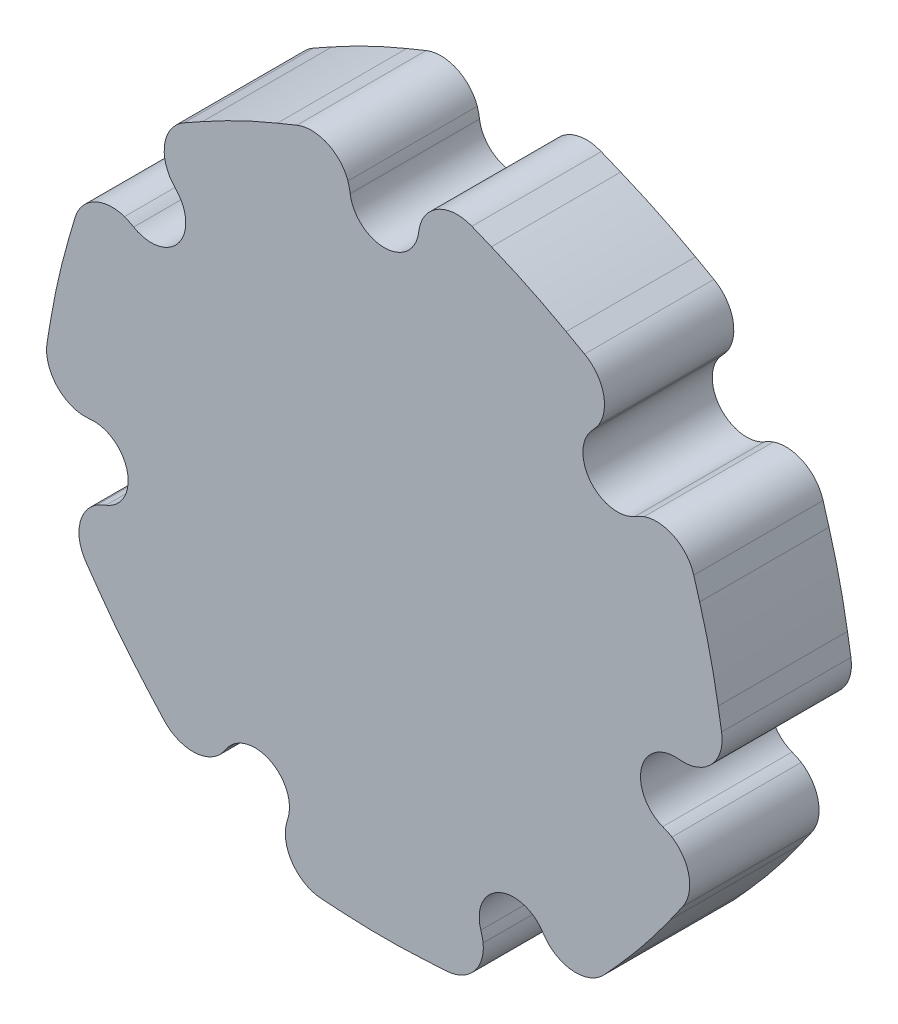
SolidWorks part; units mm, degrees
ref_plane "Piano frontale" through (0, 0, 0) normal (0, 0, 1) x (1, 0, 0)
ref_plane "Piano superiore" through (0, 0, 0) normal (0, 1, 0) x (1, 0, 0)
ref_plane "Piano destro" through (0, 0, 0) normal (1, 0, 0) x (0, 0, -1)
sketch "Schizzo1" plane through (0, 0, 0) normal (0, 0, 1) x (1, 0, 0)
  line L0 (0, 0) -> (0, 80) construction
  line L1 (-20.3041, 75.6013) -> (-33.7556, 70.0942)
  line L2 (-33.7556, 70.0942) -> (-47.2071, 64.5871) construction
  line L3 (-8, 69.15) -> (-8.4369, 70.3505)
  line L4 (8, 69.15) -> (8.4369, 70.3505)
  line L5 (0, 0) -> (-34.7107, 72.0775) construction
  line L6 (20.3041, 75.6013) -> (33.7556, 70.0942)
  line L7 (33.7556, 70.0942) -> (47.2071, 64.5871) construction
  line L8 (46.4481, 63.0111) -> (33.7556, 70.0942)
  line L9 (34.7107, 72.0775) -> (0, 0) construction
  line L10 (49.0757, 49.369) -> (49.7419, 50.4591)
  line L11 (59.0516, 36.8597) -> (60.2626, 37.2665)
  line L12 (71.7669, 31.2623) -> (75.8481, 17.3118)
  line L13 (78.2239, 2.9722) -> (75.8481, 17.3118)
  line L14 (69.1964, -7.5879) -> (70.4641, -7.429)
  line L15 (65.6361, -23.1867) -> (66.7093, -23.8799)
  line L16 (69.1877, -36.6179) -> (60.8255, -48.5067)
  line L17 (51.0956, -59.3048) -> (60.8255, -48.5067)
  line L18 (37.2108, -58.8309) -> (38.1254, -59.723)
  line L19 (22.7953, -65.7731) -> (22.9225, -67.0443)
  line L20 (14.5088, -76.9241) -> (0, -77.7987)
  line L21 (-14.5088, -76.9241) -> (0, -77.7987)
  line L22 (-22.7953, -65.7731) -> (-22.9225, -67.0443)
  line L23 (-37.2108, -58.8309) -> (-38.1254, -59.723)
  line L24 (-51.0956, -59.3048) -> (-60.8255, -48.5067)
  line L25 (-69.1877, -36.6179) -> (-60.8255, -48.5067)
  line L26 (-65.6361, -23.1867) -> (-66.7093, -23.8799)
  line L27 (-69.1964, -7.5879) -> (-70.4641, -7.429)
  line L28 (-78.2239, 2.9722) -> (-75.8481, 17.3118)
  line L29 (-71.7669, 31.2623) -> (-75.8481, 17.3118)
  line L30 (-59.0516, 36.8597) -> (-60.2626, 37.2665)
  line L31 (-49.0757, 49.369) -> (-49.7419, 50.4591)
  line L32 (-46.4481, 63.0111) -> (-33.7556, 70.0942)
  circle A0 centre (0, 0) radius 80 construction
  circle A1 centre (0, 0) radius 69.15 construction
  circle A2 centre (0, 0) radius 61.65 construction
  arc A4 (-8, 69.15) -> (8, 69.15) centre (0, 69.15) ccw
  arc A5 (-8.4369, 70.3505) -> (-20.3041, 75.6013) centre (-16.8942, 67.2723) ccw
  arc A6 (20.3041, 75.6013) -> (8.4369, 70.3505) centre (16.8942, 67.2723) ccw
  arc A7 (49.7419, 50.4591) -> (46.4481, 63.0111) centre (42.0623, 55.152) ccw
  arc A8 (49.0757, 49.369) -> (59.0516, 36.8597) centre (54.0636, 43.1143) ccw
  arc A9 (71.7669, 31.2623) -> (60.2626, 37.2665) centre (63.129, 28.7352) ccw
  arc A10 (70.4641, -7.429) -> (78.2239, 2.9722) centre (69.345, 1.5011) ccw
  arc A11 (69.1964, -7.5879) -> (65.6361, -23.1867) centre (67.4163, -15.3873) ccw
  arc A12 (69.1877, -36.6179) -> (66.7093, -23.8799) centre (61.8264, -31.4401) ccw
  arc A13 (38.1254, -59.723) -> (51.0956, -59.3048) centre (44.4095, -53.2802) ccw
  arc A14 (37.2108, -58.8309) -> (22.7953, -65.7731) centre (30.0031, -62.302) ccw
  arc A15 (14.5088, -76.9241) -> (22.9225, -67.0443) centre (13.9672, -67.9404) ccw
  arc A16 (-22.9225, -67.0443) -> (-14.5088, -76.9241) centre (-13.9672, -67.9404) ccw
  arc A17 (-22.7953, -65.7731) -> (-37.2108, -58.8309) centre (-30.0031, -62.302) ccw
  arc A18 (-51.0956, -59.3048) -> (-38.1254, -59.723) centre (-44.4095, -53.2802) ccw
  arc A19 (-66.7093, -23.8799) -> (-69.1877, -36.6179) centre (-61.8264, -31.4401) ccw
  arc A20 (-65.6361, -23.1867) -> (-69.1964, -7.5879) centre (-67.4163, -15.3873) ccw
  arc A21 (-78.2239, 2.9722) -> (-70.4641, -7.429) centre (-69.345, 1.5011) ccw
  arc A22 (-60.2626, 37.2665) -> (-71.7669, 31.2623) centre (-63.129, 28.7352) ccw
  arc A23 (-59.0516, 36.8597) -> (-49.0757, 49.369) centre (-54.0636, 43.1143) ccw
  arc A24 (-46.4481, 63.0111) -> (-49.7419, 50.4591) centre (-42.0623, 55.152) ccw
  point P14 (-11.6393, 79.1488)
  point P22 (11.6393, 79.1488)
  point P92 (0, 0)
  dimension "D1" = 160
  dimension "D2" = 138.3
  dimension "D3" = 123.3
  dimension "D10" = 16
  dimension "D5" = 9
  dimension "D8" = 9
  dimension "D4" = 51.429
  dimension "D6" = 20
  dimension "D7" = 20
  dimension "D9" = 7
  dimension "D12" = 25.714
extrude "Estrusione-Estrusione1" add sketch "Schizzo1" along normal blind 30 contours L32 A24 L31 A23 L30 A22 L29 L28 A21 L27 A20 L26 A19 L25 L24 A18 L23 A17 L22 A16 L21 L20 A15 L19 A14 L18 A13 L17 L16 A12 L15 A11 L14 A10 L13 L12 A9 L11 A8 L10 A7 L8 L6 A6 L4 A4 L3 A5 L1 region at (0, 0, 0)
fillet "Raccordo1" radius 15 14 edges at (8, 69.15, 15) (-49.0757, 49.369, 15) (-59.0516, 36.8597, 15) (-69.1964, -7.5879, 15) (-65.6361, -23.1867, 15) (-37.2108, -58.8309, 15) (-22.7953, -65.7731, 15) (22.7953, -65.7731, 15) (37.2108, -58.8309, 15) (65.6361, -23.1867, 15) (69.1964, -7.5879, 15) (59.0516, 36.8597, 15) (49.0757, 49.369, 15) (-8, 69.15, 15)
fillet "Raccordo2" radius 160 7 edges at (75.8481, 17.3118, 15) (0, -77.7987, 15) (-60.8255, -48.5067, 15) (-75.8481, 17.3118, 15) (-33.7556, 70.0942, 15) (33.7556, 70.0942, 15) (60.8255, -48.5067, 15)
